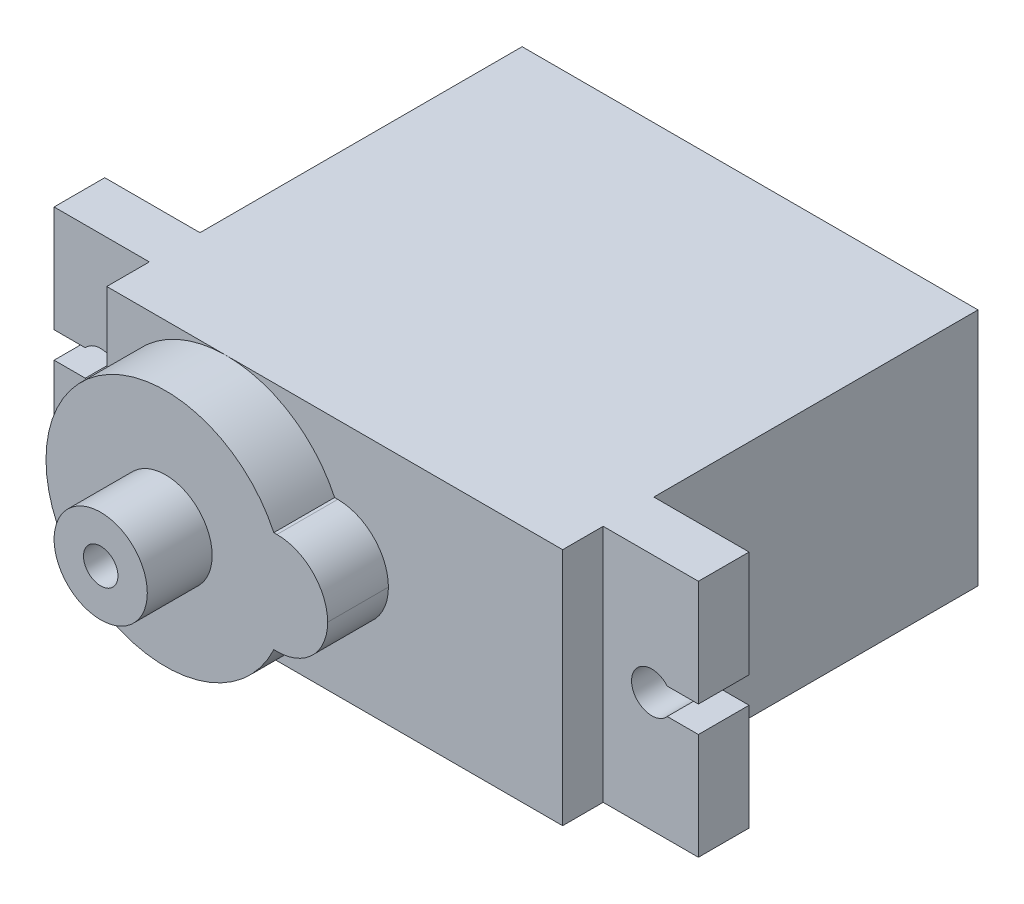
SolidWorks part; units mm, degrees
ref_plane "Front Plane" through (0, 0, 0) normal (0, 0, 1) x (1, 0, 0)
ref_plane "Top Plane" through (0, 0, 0) normal (0, 1, 0) x (1, 0, 0)
ref_plane "Right Plane" through (0, 0, 0) normal (1, 0, 0) x (0, 0, -1)
sketch "Sketch1" plane through (0, 0, 0) normal (0, 0, 1) x (1, 0, 0)
  line L1 (-8.0991, -1.4214) -> (14.4009, -1.4214)
  line L2 (-8.0991, -1.4214) -> (-8.0991, 10.3786)
  line L3 (-8.0991, 10.3786) -> (14.4009, 10.3786)
  line L4 (14.4009, -1.4214) -> (14.4009, 10.3786)
  dimension "D1" = 11.8
  dimension "D2" = 22.5
extrude "Boss-Extrude1" add sketch "Sketch1" along normal blind 26.7
sketch "Sketch2" plane through (14.4009, 0, 0) normal (1, 0, 0) x (0, 0, -1)
  line L0 (-18.5, 10.3786) -> (-18.5, -1.4214)
  line L1 (-26.7, 10.3786) -> (0, 10.3786) construction
  line L2 (-26.7, -1.4214) -> (0, -1.4214) construction
  line L3 (-16, 10.3786) -> (-16, -1.4214)
  line L5 (0, -1.4214) -> (0, 10.3786) construction
  line L6 (-18.5, 10.3786) -> (-16, 10.3786)
  line L7 (-16, -1.4214) -> (-18.5, -1.4214)
  dimension "D1" = 2.5
  dimension "D2" = 16
extrude "Boss-Extrude2" add sketch "Sketch2" along normal blind 4.7 contours L3 L7 L0 L6
sketch "Sketch5" plane through (-8.0991, 0, 0) normal (-1, 0, 0) x (0, 0, 1)
  line L0 (18.4, -1.4214) -> (18.4, 10.3786)
  line L1 (26.7, -1.4214) -> (0, -1.4214) construction
  line L2 (26.7, 10.3786) -> (0, 10.3786) construction
  line L3 (18.4, 10.3786) -> (15.9, 10.3786)
  line L4 (15.9, 10.3786) -> (15.9, -1.4214)
  line L5 (15.9, -1.4214) -> (18.4, -1.4214)
  line L6 (0, 10.3786) -> (0, -1.4214) construction
  dimension "D1" = 15.9
  dimension "D2" = 2.5
extrude "Boss-Extrude3" add sketch "Sketch5" along normal blind 4.7
sketch "Sketch6" plane through (0, 0, 26.7) normal (0, 0, 1) x (1, 0, 0)
  line L0 (-8.0991, 10.3786) -> (-8.0991, -1.4214) construction
  line L1 (-8.0991, -1.4214) -> (14.4009, -1.4214) construction
  line L2 (3.8234, 4.4786) -> (5.8009, 6.9786) construction
  line L8 (3.1451, 1.9786) -> (5.8009, 1.9786)
  line L10 (3.1451, 6.9786) -> (5.8009, 6.9786)
  line L11 (5.8009, 1.9786) -> (5.8009, 6.9786)
  line L13 (3.8234, 4.4786) -> (5.8009, 1.9786) construction
  arc A1 (3.1451, 6.9786) -> (3.1451, 1.9786) centre (-2.1991, 4.4786) ccw
  arc A2 (3.6988, 4.3212) -> (3.6988, 4.6361) centre (-2.1991, 4.4786) ccw
  point P7 (3.8234, 4.4786)
  line M2 (-8.0991, 10.3786) -> (-8.0991, -1.4214)
  line M3 (-8.0991, -1.4214) -> (14.4009, -1.4214)
  line M4 (14.4009, -1.4214) -> (14.4009, 10.3786)
  line M5 (14.4009, 10.3786) -> (-8.0991, 10.3786)
  dimension "D1" = 11.8
  dimension "D2" = 5.9
  dimension "D3" = 5.9
  dimension "D4" = 5
  dimension "D5" = 5.9
  dimension "D6" = 8
extrude "Cut-Extrude1" cut sketch "Sketch6" against normal blind 6.2 contours A1 L10 L11 L8 M3 M4 M5 | A1 M2 M3 | A1 M5 M2 region at (8.6698, 4.4786, 26.7) region at (-6.7812, -0.1035, 26.7) region at (-6.7812, 9.0608, 26.7)
fillet "Fillet1" radius 2.5 1 edges at (5.8009, 1.9786, 23.6)
fillet "Fillet2" radius 2.5 1 edges at (5.8009, 6.9786, 23.6)
extrude "Cut-Extrude2" cut sketch "Sketch6<3>" against normal blind 3.2 contours L10 A1 L8 L11 region at (-1.5517, 4.4786, 26.7)
sketch "Sketch6<3>" plane through (0, 0, 26.7) normal (0, 0, 1) x (1, 0, 0) same geometry as "Sketch6"
sketch "Sketch7" plane through (0, 0, 23.5) normal (0, 0, 1) x (1, 0, 0)
  line L0 (-8.0991, -1.4214) -> (-8.0991, 10.3786) construction
  line L1 (14.4009, 10.3786) -> (-2.1991, 10.3786) construction
  circle A0 centre (-2.1991, 4.4786) radius 2.3
  circle A1 centre (-2.1991, 4.4786) radius 0.85
  dimension "D1" = 4.6
  dimension "D4" = 1.7
  dimension "D2" = 5.9
  dimension "D3" = 5.9
extrude "Boss-Extrude4" add sketch "Sketch7" along normal blind 3.2
sketch "Sketch11" plane through (0, 0, 18.4) normal (0, 0, 1) x (1, 0, 0)
  line L0 (-12.7991, -1.4214) -> (-12.7991, 10.3786) construction
  line L1 (-12.7991, -1.4214) -> (-8.0991, -1.4214) construction
  line L2 (-12.8658, 3.8286) -> (-11.259, 3.8286)
  line L3 (-12.8658, 3.8286) -> (-12.8658, 5.1286)
  line L4 (-12.8658, 5.1286) -> (-11.259, 5.1286)
  line L6 (-12.8658, 3.8286) -> (-11.259, 5.1286) construction
  line L7 (-12.8658, 5.1286) -> (-11.259, 3.8286) construction
  arc A0 (-11.259, 3.8286) -> (-11.259, 5.1286) centre (-10.4991, 4.4786) ccw
  point P4 (-12.0624, 4.4786)
  dimension "D1" = 2
  dimension "D2" = 2.3
  dimension "D3" = 1.3
  dimension "D4" = 5.9
  dimension "D5" = 5.9
extrude "Cut-Extrude3" cut sketch "Sketch11" against normal blind 2.5
sketch "Sketch12" plane through (0, 0, 18.5) normal (0, 0, 1) x (1, 0, 0)
  line L0 (19.1009, 10.3786) -> (14.4009, 10.3786) construction
  line L1 (19.1009, 10.3786) -> (19.1009, -1.4214) construction
  line L3 (17.5608, 3.8286) -> (19.1009, 3.8286)
  line L5 (17.5608, 5.1286) -> (19.1009, 5.1286)
  line L6 (19.1009, 3.8286) -> (19.1009, 5.1286)
  line L7 (17.6984, 4.0376) -> (19.1009, 5.1286) construction
  line L8 (17.6984, 4.9197) -> (19.1009, 3.8286) construction
  arc A0 (17.5608, 5.1286) -> (17.5608, 3.8286) centre (16.8009, 4.4786) ccw
  point P6 (18.2653, 4.4786)
  dimension "D1" = 2
  dimension "D2" = 5.9
  dimension "D3" = 2.3
  dimension "D4" = 1.3
  dimension "D5" = 5.9
extrude "Cut-Extrude4" cut sketch "Sketch12" against normal blind 2.5
